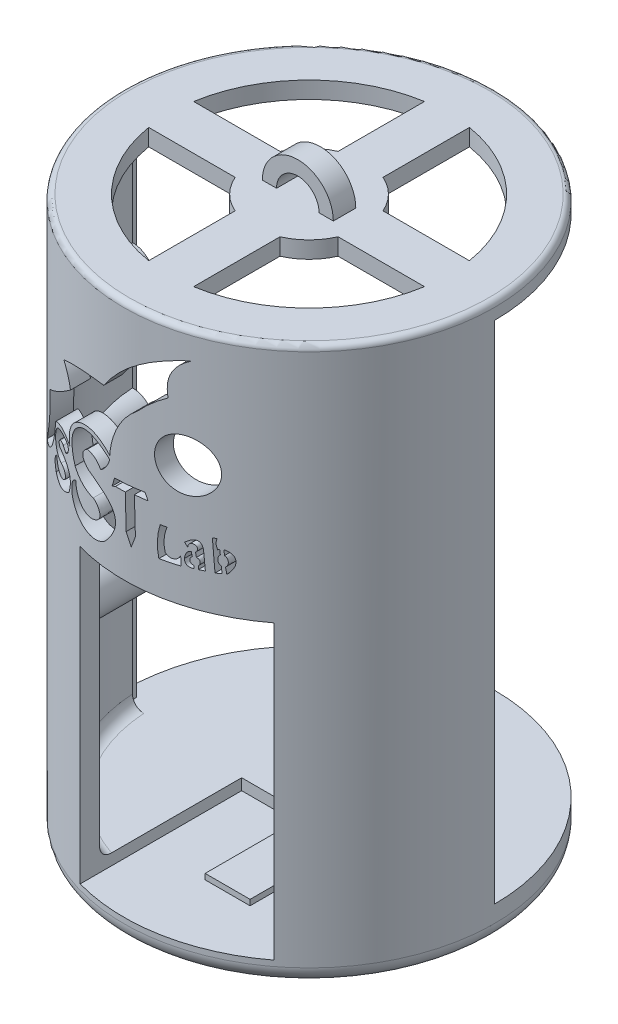
SolidWorks part; units mm, degrees
other "DetailItem1"
other "DetailItem2"
material "Default"
ref_plane "Front Plane" through (0, 0, 0) normal (0, 0, 1) x (1, 0, 0)
ref_plane "Top Plane" through (0, 0, 0) normal (0, 1, 0) x (1, 0, 0)
ref_plane "Right Plane" through (0, 0, 0) normal (1, 0, 0) x (0, 0, -1)
sketch "Sketch1" plane through (0, 0, 0) normal (0, 1, 0) x (1, 0, 0)
  circle A0 centre (0, 0) radius 33
extrude "Boss-Extrude1" add sketch "Sketch1" along normal blind 3
sketch "Sketch2" plane through (0, 0, 0) normal (0, -1, 0) x (1, 0, 0)
  line L5 (-33, 0) -> (-30.7372, 0)
  line L6 (33, 0) -> (30.7372, 0)
  line L7 (0, 11.2686) -> (0, -5.695) construction
  line L9 (-30.7372, 0) -> (-30.7372, 1.8)
  line L10 (-30.7372, 1.8) -> (-29.6372, 1.8)
  line L14 (30.7372, 0) -> (30.7372, 1.8)
  line L15 (30.7372, 1.8) -> (29.6372, 1.8)
  arc A1 (33, 0) -> (-33, 0) centre (0, 0) ccw
  arc A2 (29.6372, 1.8) -> (-29.6372, 1.8) centre (0, 0) ccw
  dimension "D2" = 1.1
  dimension "D3" = 1.1
extrude "Boss-Extrude2" add sketch "Sketch2" along normal blind 90
sketch "Sketch3" plane through (0, -90, 0) normal (0, -1, 0) x (1, 0, 0)
  line L5 (30.7372, 0) -> (33, 0) construction
  line L10 (31.8686, 0) -> (29.6826, 0)
  line L11 (31.8686, 0) -> (31.8686, 0.7423)
  line L12 (31.8686, 0.7423) -> (29.6826, 0.7423)
  line L13 (29.6826, 0) -> (29.6826, 0.7423)
  line L19 (-30.9932, 0) -> (-29.8932, 0)
  line L20 (-30.9932, 0) -> (-30.9932, 1.8)
  line L21 (-30.9932, 1.8) -> (-29.8932, 1.8)
  line L22 (-29.8932, 0) -> (-29.8932, 1.8)
  arc A1 (29.6372, 1.8) -> (-29.6372, 1.8) centre (0, 0) ccw construction
  dimension "D1" = 1.8
  dimension "D2" = 1.1
fillet "Fillet1" radius 1 1 edges at (0, 0, 29.6918)
fillet "Fillet2" radius 1 1 edges at (0, 3, 33)
ref_plane "Plane1" through (0, 3, 0) normal (0, 1, 0) x (1, 0, 0)
sketch "Sketch5" plane through (0, 3, 0) normal (0, 1, 0) x (1, 0, 0)
  line L5 (9.1652, 4) -> (24.5508, 4)
  line L19 (-4, 9.1652) -> (-4, 24.5508)
  line L21 (4, 9.1652) -> (4, 24.5508)
  line L22 (9.1652, -4) -> (24.5508, -4)
  line L23 (4, -9.1652) -> (4, -24.5508)
  line L24 (-4, -9.1652) -> (-4, -24.5508)
  line L25 (-9.1652, -4) -> (-24.5508, -4)
  line L26 (-9.1652, 4) -> (-24.5508, 4)
  circle A0 centre (0, 0) radius 32
  circle A1 centre (0, 0) radius 10
  circle A2 centre (0, 0) radius 24.8745
  point P5 (10, 0)
  point P6 (0, 10)
  dimension "D1" = 8
  dimension "D2" = 4
extrude "Cut-Extrude2" cut sketch "Sketch5" against normal blind 10 contours A2 A1 | A2 A1 | A2 A1 | A2 A1 region at (12.6734, 3, -12.6734) region at (12.6734, 3, 12.6734) region at (-12.6734, 3, -12.6734) region at (-12.6734, 3, 12.6734)
sketch "Sketch8" plane through (0, 0, 0) normal (0, 0, 1) x (1, 0, 0)
  line L0 (36.3, 3) -> (-36.3, 3) construction
  line L1 (3.7868, 3) -> (6.3209, 3)
  line L2 (-3.7868, 3) -> (-6.3209, 3)
  arc A0 (6.3209, 3) -> (-6.3209, 3) centre (0, 3) ccw
  arc A1 (3.7868, 3) -> (-3.7868, 3) centre (0, 3) ccw
extrude "Boss-Extrude3" add sketch "Sketch8" along normal mid plane 4
sketch "Sketch9" plane through (0, -90, 0) normal (0, -1, 0) x (1, 0, 0)
  circle A0 centre (0, 0) radius 33
extrude "Boss-Extrude5" add sketch "Sketch9" along normal blind 6
fillet "Fillet5" radius 2 1 edges at (0, -90, 29.6918)
ref_plane "Plane9" through (0, 0, 1.8) normal (0, 0, 1) x (1, 0, 0)
sketch "Sketch23" plane through (0, 0, 1.8) normal (0, 0, 1) x (1, 0, 0)
  line L0 (30.7372, 0) -> (30.7372, -22.4) construction
  line L1 (28.6353, 0) -> (30.7372, 0) construction
  line L2 (30.7372, -90) -> (30.7372, 0) construction
  line L3 (30.7372, -22.4) -> (30.7372, -44.8) construction
  line L4 (0, 0) -> (0, -62.9284) construction
  line L5 (29.6372, -88) -> (29.6372, -1) construction
  line L6 (29.6372, -18.4) -> (29.6372, -26.4)
  line L7 (29.6372, -40.8) -> (29.6372, -48.8)
  line L8 (-30.7372, -22.4) -> (-30.7372, -44.8) construction
  line L9 (-30.7372, 0) -> (-30.7372, -22.4) construction
  line L10 (-29.6372, -40.8) -> (-29.6372, -48.8)
  line L11 (-29.6372, -18.4) -> (-29.6372, -26.4)
  line L12 (30.7372, 0) -> (33, 0) construction
  arc A0 (29.6372, -26.4) -> (29.6372, -18.4) centre (29.6372, -22.4) cw
  arc A1 (29.6372, -48.8) -> (29.6372, -40.8) centre (29.6372, -44.8) cw
  circle A2 centre (28.1372, -22.4) radius 1
  circle A3 centre (28.1372, -44.8) radius 1
  circle A4 centre (-28.1372, -44.8) radius 1
  circle A5 centre (-28.1372, -22.4) radius 1
  arc A6 (-29.6372, -48.8) -> (-29.6372, -40.8) centre (-29.6372, -44.8) ccw
  arc A7 (-29.6372, -26.4) -> (-29.6372, -18.4) centre (-29.6372, -22.4) ccw
  dimension "D4" = 1.5
  dimension "D3" = 1.5
  dimension "D5" = 22.4
  dimension "D9" = 2
  dimension "D10" = 2
  dimension "D11" = 4
  dimension "D12" = 4
  dimension "D2" = 22.4
extrude "Boss-Extrude6" add sketch "Sketch23" along normal up to surface contours A1 L7 | A0 L6 region at (29.5478, -22.4, 1.8) region at (29.5478, -44.8, 1.8) up to face at (0, -44.5, 15.7459)
sketch "Sketch25" plane through (0, 0, 1.8) normal (0, 0, 1) x (1, 0, 0)
  line L0 (30.7372, 0) -> (30.7372, -67.2) construction
  line L1 (28.6353, 0) -> (30.7372, 0) construction
  line L2 (30.7372, -90) -> (30.7372, 0) construction
  line L3 (29.6372, -88) -> (29.6372, -48.8) construction
  line L4 (29.6372, -62.8) -> (29.6372, -71.6)
  arc A0 (29.6372, -71.6) -> (29.6372, -62.8) centre (29.6372, -67.2) cw
  arc A1 (29.6372, -40.8) -> (29.6372, -48.8) centre (29.6372, -44.8) ccw construction
  dimension "D2" = 22.4
  dimension "D1" = 67.2
extrude "Boss-Extrude7" add sketch "Sketch25" along normal up to surface up to face at (13.8247, -38.9403, 12.0571)
sketch "Sketch27" plane through (0, 0, 1.8) normal (0, 0, -1) x (-1, 0, 0)
  line L0 (-29.6372, -62.8) -> (-29.6372, -48.8) construction
  circle A0 centre (-28.1372, -67.2) radius 1
  circle A1 centre (-28.1372, -44.8) radius 1 construction
  dimension "D1" = 22.4
  dimension "D2" = 1.5
  dimension "D3" = 2
extrude "Cut-Extrude3" cut sketch "Sketch27" against normal blind 3
mirror "Mirror8" about plane through (0, 0, 0) normal (1, 0, 0) of "Cut-Extrude3", "Boss-Extrude7"
sketch "Sketch28" plane through (0, 0, 1.8) normal (0, 0, 1) x (1, 0, 0)
  line L0 (28.1372, -44.8) -> (-34.2493, -44.8) construction
  line L1 (28.1372, -22.4) -> (-41.9407, -22.4) construction
  line L2 (-29.6372, -62.8) -> (-29.6372, -1) construction
  line L3 (-29.6372, -18.4) -> (-29.6372, -26.4)
  line L4 (-29.6372, -40.8) -> (-29.6372, -48.8)
  arc A0 (-29.6372, -26.4) -> (-29.6372, -18.4) centre (-29.6372, -22.4) ccw
  arc A1 (-29.6372, -48.8) -> (-29.6372, -40.8) centre (-29.6372, -44.8) ccw
  circle A2 centre (-28.1372, -22.4) radius 1
  circle A3 centre (-28.1372, -44.8) radius 1
  dimension "D1" = 2
  dimension "D2" = 1.5
  dimension "D3" = 2
  dimension "D4" = 1.5
  dimension "D5" = 22.4
  dimension "D6" = 4
  dimension "D7" = 4
extrude "Boss-Extrude8" add sketch "Sketch28" along normal up to surface up to face at (9.2164, -48.4259, 10.9404)
ref_plane "Plane10" through (0, 0, 33) normal (0, 0, 1) x (1, 0, 0)
sketch "Sketch29" plane through (0, 0, 33) normal (0, 0, 1) x (1, 0, 0)
  line L20 (10.3497, -31.2602) -> (10.5044, -32.0234)
  line L21 (14.9323, -33.4375) -> (14.8344, -33.4516)
  line L22 (13.0791, -28.3186) -> (13.661, -28.2824)
  line L23 (13.4116, -33.6564) -> (13.0791, -28.3186)
  line L24 (9.9144, -30.8015) -> (9.4598, -30.1414)
  line L25 (12.1999, -33.6878) -> (11.9606, -30.4214)
  line L26 (11.2995, -33.7537) -> (12.1999, -33.6878)
  line L27 (8.96, -34.0019) -> (8.9155, -32.284)
  line L28 (5.7528, -34.085) -> (8.96, -34.0019)
  line L29 (5.9604, -28.7669) -> (6.9783, -28.7405)
  line L30 (-2.1439, -26.6424) -> (-1.6675, -25.1441)
  line L31 (-1.5031, -26.3504) -> (-2.1439, -26.6424)
  line L32 (0.2805, -26.3042) -> (-1.5031, -26.3504)
  line L33 (0.4366, -32.3279) -> (0.2805, -26.3042)
  line L34 (1.3166, -34.2591) -> (0.4366, -32.3279)
  line L35 (2.0181, -32.3831) -> (1.3166, -34.2591)
  line L36 (1.8515, -25.9516) -> (2.0181, -32.3831)
  line L37 (3.7168, -25.9033) -> (1.8515, -25.9516)
  line L38 (4.076, -25.894) -> (3.7168, -25.9033)
  line L39 (3.6049, -24.7863) -> (4.076, -25.894)
  line L40 (-1.6675, -25.1441) -> (3.6049, -24.7863)
  line L41 (10.9201, -31.1875) -> (11.0474, -31.9577)
  line L42 (10.7263, -33.3003) -> (10.7263, -33.7957)
  line L43 (11.2995, -33.1475) -> (11.2995, -33.7537)
  line L44 (14.0618, -30.684) -> (13.9798, -29.8728)
  line L45 (14.4991, -29.7895) -> (14.5553, -30.6602)
  line L46 (14.1861, -32.3831) -> (14.2604, -33.5342)
  line L47 (14.6806, -32.3831) -> (14.8344, -33.4516)
  line L48 (14.2604, -33.5342) -> (13.4116, -33.6564)
  arc A10 (-13.5863, -14.2814) -> (-11.5825, -17.5685) centre (-17.9326, -19.1853) cw
  arc A11 (11.0474, -31.9577) -> (11.2995, -33.1475) centre (10.8521, -32.6207) cw
  arc A12 (-19.4143, -23.4894) -> (-22.0921, -33.5004) centre (-35.3063, -24.6022) cw
  arc A13 (9.9144, -30.8015) -> (10.9201, -31.1875) centre (10.5474, -30.6556) cw
  arc A14 (6.9783, -28.7405) -> (6.7006, -32.7283) centre (13.3477, -31.1875) ccw
  arc A15 (8.9155, -32.284) -> (6.7006, -32.7283) centre (7.7211, -32.0723) cw
  circle A16 centre (9.6565, -18.228) radius 4.5597
  arc A17 (-2.5847, -22.7927) -> (-4.3975, -25.3508) centre (-7.1045, -21.5111) cw
  arc A18 (2.4111, -12.7835) -> (-2.5029, -21.3522) centre (10.5264, -23.1309) ccw
  arc A19 (7.1332, -8.7573) -> (2.4111, -12.7835) centre (19.9884, -28.6167) ccw
  arc A20 (10.7263, -33.3003) -> (10.5044, -32.0234) centre (10.8521, -32.6207) cw
  ellipse E0 centre (14.3805, -31.5273) end of major axis (14.4867, -32.4542) minor radius 0.631 (14.1861, -32.3831) -> (14.0618, -30.684) cw
  ellipse E1 centre (14.3805, -31.5273) end of major axis (14.4867, -32.4542) minor radius 0.631 (14.5553, -30.6602) -> (14.6806, -32.3831) cw
  spline S0 degree 3 poles (14.976, -29.9092) (15.7506, -30.2888) (16.1523, -31.6544) (15.5212, -32.7221) (14.9323, -33.4375) knots 0 0 0 0 0.414034 1 1 1 1
  spline S1 degree 3 poles (14.4991, -29.7895) (14.6597, -29.7975) (14.8186, -29.8374) (14.976, -29.9092) knots 0.606507 0.606507 0.606507 0.606507 1 1 1 1
  spline S32 degree 3 poles (-12.2921, -26.63) (-13.2175, -25.9227) (-15.6875, -25.6495) (-17.0061, -28.6402) (-16.2923, -30.6859) (-14.4343, -30.858) knots 0 0 0 0 0.411956 0.546967 1 1 1 1
  spline S33 degree 2 poles (-2.5029, -21.3522) (-2.5523, -21.745) (-2.5868, -22.1393) knots 0 0 0 1 1 1
  spline S34 degree 2 poles (-16.1582, -30.9026) (-17.404, -31.9012) (-16.3536, -33.674) knots 0 0 0 1 1 1
  spline S35 degree 2 poles (-15.6598, -32.2521) (-15.9882, -31.6057) (-16.1582, -30.9026) knots 0 0 0 1 1 1
  spline S36 degree 2 poles (-13.2686, -32.5726) (-14.4696, -33.5705) (-15.6598, -32.2521) knots 0 0 0 1 1 1
  spline S37 degree 3 poles (-14.4343, -30.858) (-13.6663, -30.9158) (-12.6594, -31.5718) (-13.2686, -32.5726) knots 0 0 0 0 1 1 1 1
  spline S38 degree 3 poles (-10.0785, -30.4845) (-10.8982, -30.7145) (-11.4749, -32.2811) (-10.2059, -36.3766) (-5.7157, -37.6351) (-3.563, -35.9022) knots 0 0 0 0 0.18147 0.363648 1 1 1 1
  spline S39 degree 3 poles (-5.9901, -30.6259) (-5.2188, -30.82) (-3.7027, -32.8178) (-7.6665, -35.0398) (-10.1905, -32.5518) (-10.0785, -30.4845) knots 0 0 0 0 0.256771 0.45536 1 1 1 1
  spline S40 degree 3 poles (-2.5868, -22.1393) (-3.4905, -21.3123) (-7.4736, -18.8372) (-12.7733, -22.5557) (-11.7646, -26.3044) knots 0 0 0 0 0.283429 1 1 1 1
  spline S41 degree 2 poles (-12.9411, -28.2519) (-11.9486, -27.7855) (-12.2921, -26.63) knots 0 0 0 1 1 1
  spline S42 degree 1 poles (-13.7789, -27.6421) (-12.9411, -28.2519) knots 0 0 1 1
  spline S43 degree 3 poles (-14.8211, -28.7766) (-15.2903, -28.6729) (-15.322, -27.8606) (-14.5854, -27.4739) (-14.1485, -27.4232) (-13.7789, -27.6421) knots 0 0 0 0 0.517246 0.524946 1 1 1 1
  spline S44 degree 2 poles (-12.0095, -33.637) (-10.4824, -29.9072) (-14.8211, -28.7766) knots 0 0 0 1 1 1
  spline S46 degree 2 poles (13.7453, -29.9798) (13.8631, -29.9155) (13.9798, -29.8728) knots 0 0 0 0.186735 0.186735 0.186735
  spline S47 degree 2 poles (13.661, -28.2824) (13.3929, -29.1135) (13.7453, -29.9798) knots 0 0 0 1 1 1
  spline S48 degree 2 poles (11.9606, -30.4214) (11.5225, -28.3354) (9.4598, -30.1414) knots 0 0 0 1 1 1
  spline S49 degree 3 poles (9.4313, -32.6575) (9.4516, -33.4781) (9.8833, -33.8575) (10.7263, -33.7957) knots 0 0 0 0 1 1 1 1
  spline S50 degree 3 poles (10.3497, -31.2602) (9.8092, -31.3698) (9.5031, -31.8355) (9.4313, -32.6575) knots 0.205596 0.205596 0.205596 0.205596 1 1 1 1
  spline S51 degree 2 poles (5.9604, -28.7669) (5.2109, -31.4056) (5.7528, -34.085) knots 0 0 0 1 1 1
  spline S52 degree 3 poles (-7.284, -23.8933) (-6.1127, -23.9767) (-5.358, -23.9842) (-4.3975, -25.3508) knots 0 0 0 0 1 1 1 1
  spline S53 degree 2 poles (-7.1125, -26.897) (-9.5434, -25.4113) (-7.284, -23.8933) knots 0 0 0 1 1 1
  spline S54 degree 2 poles (-3.563, -35.9022) (1.9227, -30.1372) (-7.1125, -26.897) knots 0 0 0 1 1 1
  spline S55 degree 2 poles (-10.3098, -28.3991) (-8.6829, -30.3656) (-5.9901, -30.6259) knots 0 0 0 1 1 1
  spline S56 degree 2 poles (-16.3536, -33.674) (-14.5512, -35.6154) (-12.0095, -33.637) knots 0 0 0 1 1 1
  spline S57 degree 3 poles (-16.5512, -26.0468) (-17.003, -29.2318) (-18.2453, -32.9853) (-22.0921, -33.5004) knots 0 0 0 0 1 1 1 1
  spline S58 degree 3 poles (-11.7646, -26.3044) (-12.2558, -25.9998) (-13.6837, -24.9224) (-15.6674, -25.4046) (-16.5512, -26.0468) knots 0 0 0 0 0.341852 1 1 1 1
  spline S59 degree 2 poles (-11.5825, -17.5685) (-15.391, -20.6698) (-19.4143, -23.4894) knots 0 0 0 1 1 1
  spline S60 degree 3 poles (-2.5847, -22.7927) (-4.0492, -21.6566) (-7.5882, -20.067) (-11.8223, -23.811) (-11.0194, -27.0452) (-10.3098, -28.3991) knots 0 0 0 0 0.40613 0.663915 1 1 1 1
  spline S61 degree 2 poles (-3.7822, -11.9871) (-8.9719, -11.9315) (-13.5863, -14.2814) knots 0 0 0 1 1 1
  spline S62 degree 2 poles (10.423, -1.8621) (1.5693, -4.4415) (-3.7822, -11.9871) knots 0 0 0 1 1 1
  spline S63 degree 2 poles (7.1332, -8.7573) (6.3115, -4.2857) (10.423, -1.8621) knots 0 0 0 1 1 1
extrude "Cut-Extrude4" cut sketch "Sketch29" against normal through all
ref_plane "Plane14" through (0, 0, 33) normal (0, 0, 1) x (1, 0, 0)
sketch "Sketch38" plane through (0, 0, 33) normal (0, 0, 1) x (1, 0, 0)
  line L1 (-9, -92) -> (20, -92)
  line L2 (-9, -92) -> (-9, -40)
  line L3 (-9, -40) -> (20, -40)
  line L4 (20, -92) -> (20, -40)
  line L5 (0, 0) -> (0, -95) construction
  dimension "D1" = 52
  dimension "D2" = 29
  dimension "D3" = 20
extrude "Cut-Extrude5" cut sketch "Sketch38" against normal blind 30
sketch "Sketch43" plane through (0, -92, 0) normal (0, 1, 0) x (1, 0, 0)
  line L0 (-9, -3) -> (-9, -31.749)
  line L1 (-9, -3) -> (20, -3)
  line L2 (20, -3) -> (20, -26.2488)
  arc A0 (20, -26.2488) -> (-9, -31.749) centre (0, 0) cw
  arc A1 (20, -21.7483) -> (-9, -28.2251) centre (-0.6727, 2.6516) cw
sketch "Sketch44" plane through (0, -92, 0) normal (0, 1, 0) x (1, 0, 0)
  line L0 (-9, -3) -> (5.5, -3) construction
  line L1 (-9, -3) -> (20, -3) construction
  line L2 (9.5, -20) -> (1.5, -20)
  line L3 (1.5, -3) -> (9.5, -3)
  line L4 (1.5, -3) -> (1.5, -20)
  line L6 (9.5, -3) -> (9.5, -20)
  point P10 (5.5, -3)
  dimension "D1" = 8
  dimension "D2" = 17
extrude "Boss-Extrude10" add sketch "Sketch44" along normal blind 1
fillet "Fillet3" radius 3 1 edges at (0, -96, -33)
ref_plane "Plane2" through (0, 0, 0.75) normal (0, 0, 1) x (1, 0, 0)
ref_plane "Plane4" through (0, 0, 0) normal (1, 0, 0) x (0, 0, -1)
ref_plane "Plane5" through (0, 0, 0) normal (1, 0, 0) x (0, 0, -1)
